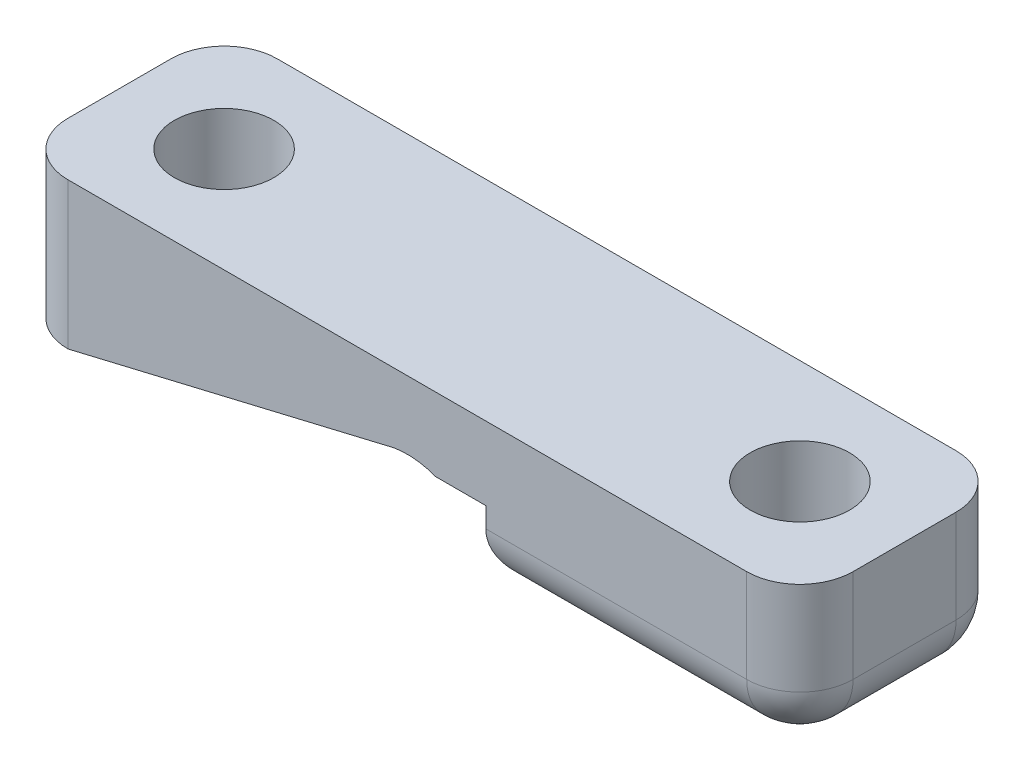
SolidWorks part; units mm, degrees
ref_plane "Front Plane" through (0, 0, 0) normal (0, 0, 1) x (1, 0, 0)
ref_plane "Top Plane" through (0, 0, 0) normal (0, 1, 0) x (1, 0, 0)
ref_plane "Right Plane" through (0, 0, 0) normal (1, 0, 0) x (0, 0, -1)
sketch "Sketch1" plane through (0, 0, 0) normal (0, 0, 1) x (1, 0, 0)
  line L1 (0, 0) -> (37.5, 0)
  line L2 (0, 0) -> (0, 7)
  line L3 (0, 7) -> (37.5, 7)
  line L4 (37.5, 0) -> (37.5, 7)
  dimension "D1" = 37.5
  dimension "D2" = 7
extrude "Boss-Extrude1" add sketch "Sketch1" along normal blind 10
sketch "Sketch2" plane through (0, 0, 10) normal (0, 0, 1) x (1, 0, 0)
  line L0 (0, 0) -> (37.5, 0) construction
  circle A0 centre (18.75, 0) radius 3.75
  dimension "D1" = 7.5
extrude "Cut-Extrude1" cut sketch "Sketch2" against normal through all both and the other way through all
fillet "Fillet1" radius 2.54 4 edges at (0, 3.5, 0) (37.5, 3.5, 0) (37.5, 3.5, 10) (0, 3.5, 10)
sketch "Sketch3" plane through (0, 7, 0) normal (0, 1, 0) x (1, 0, 0)
  line L0 (0, -5) -> (5, -5)
  line L1 (0, -7.46) -> (0, -2.54) construction
  line L2 (5, -5) -> (32.5, -5)
  line L3 (32.5, -5) -> (37.5, -5)
  line L4 (37.5, -7.46) -> (37.5, -2.54) construction
  point P9 (5, -5)
  point P10 (32.5, -5)
  dimension "D1" = 5
  dimension "D2" = 5
hole_wizard "Ø4.0mm Dowel Hole1" positions "Sketch4" profile "Sketch5" hole size "Ø4.0" standard "ANSI Metric" end condition through all
sketch "Sketch4" plane through (0, 7, 0) normal (0, 1, 0) x (1, 0, 0)
  point P0 (5, -5)
  point P3 (32.5, -5)
sketch "Sketch5" plane through (5, 7, 5) normal (1, 0, 0) x (0, 0, 1)
  line L0 (0, 0) -> (0, 7)
  line L1 (0, 7) -> (2.375, 7)
  line L2 (2.375, 7) -> (2.375, 0)
  line L5 (2.375, 0) -> (0, 0)
  line L11 (0, -6.35) -> (0, 107.95) construction
  dimension "Thru Hole Dia." = 4.75
  dimension "Thru Hole Depth" = 7
sketch "Sketch6" plane through (0, 0, 0) normal (0, 0, -1) x (-1, 0, 0)
  line L0 (-2.54, 0) -> (-18.1009, 3.6934)
  line L1 (-18.1009, 3.6934) -> (-18.1009, 0)
  line L2 (-18.1009, 0) -> (-2.54, 0)
  arc A1 (-15, 0) -> (-22.5, 0) centre (-18.75, 0) ccw construction
extrude "Cut-Extrude2" cut sketch "Sketch6" against normal through all both and the other way through all
sketch "Sketch7" plane through (0, 0, 0) normal (0, -1, 0) x (1, 0, 0)
  line L0 (20.085, 10) -> (20.085, 0)
  line L1 (22.5, 10) -> (17.6701, 10) construction
  line L2 (17.6701, 0) -> (22.5, 0) construction
  line L3 (20.085, 0) -> (30.7341, 0)
  line L4 (22.5, 10) -> (20.085, 10)
  circle A0 centre (30.7341, 8.39) radius 8.39
  line M2 (22.5, 0) -> (34.96, 0)
  line M7 (22.5, 10) -> (22.5, 0)
extrude "Cut-Extrude3" cut sketch "Sketch7" against normal blind 3.5 contours A0 M7 M2 | A0 L4 L0 L3 M7 region at (21.2764, 0, 4.9523) region at (24.365, 0, 1.7276)
fillet "Fillet2" radius 2.54 6 edges at (28.73, 0, 10) (36.7561, 0, 9.2561) (37.5, 0, 5) (36.7561, 0, 0.7439) (32.8471, 0, 0) (25.401, 0, 1.9131)
ref_plane "Plane1" through (18.75, 0, 0) normal (1, 0, 0) x (0, 0, -1)
mirror "Mirror1" [suppressed] about plane through (18.75, 0, 0) normal (1, 0, 0)
